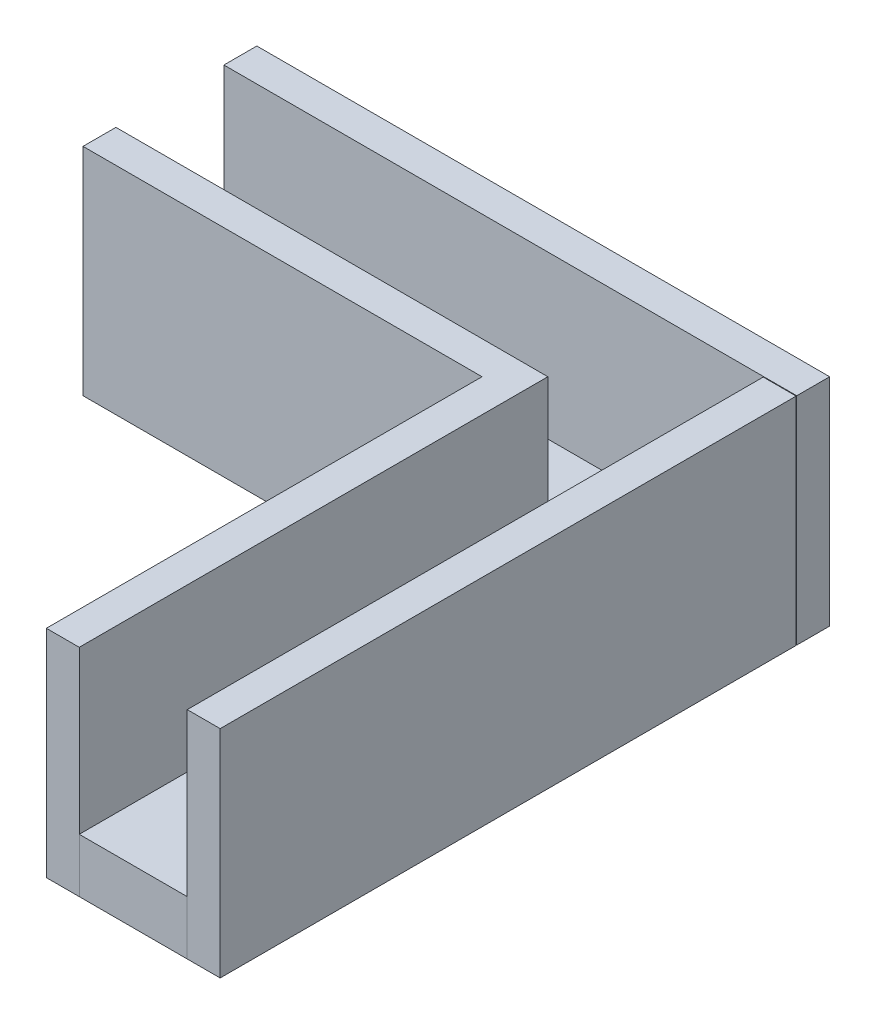
SolidWorks part; units mm, degrees
ref_plane "Front Plane" through (0, 0, 0) normal (0, 0, 1) x (1, 0, 0)
ref_plane "Top Plane" through (0, 0, 0) normal (0, 1, 0) x (1, 0, 0)
ref_plane "Right Plane" through (0, 0, 0) normal (1, 0, 0) x (0, 0, -1)
sketch "Sketch1" plane through (0, 0, 0) normal (0, 1, 0) x (1, 0, 0)
  line L5 (-12.5, 2.5) -> (12.5, -2.5) construction
  line L6 (-12.5, -2.5) -> (12.5, 2.5) construction
  line L7 (12.5, -2.5) -> (7.5, -2.5)
  line L8 (12.5, -2.5) -> (12.5, -24.198)
  line L9 (12.5, -24.198) -> (7.5, -24.198)
  line L10 (7.5, -2.5) -> (7.5, -24.198)
  line L11 (12.5, -24.198) -> (14.024, -24.198)
  line L12 (12.5, -24.198) -> (12.5, 2.472)
  line L13 (12.5, 2.472) -> (14.024, 2.472)
  line L14 (14.024, -24.198) -> (14.024, 2.472)
  line L19 (7.5, -2.5) -> (-12.5, -2.5)
  line L20 (7.5, -2.5) -> (7.5, -4.024)
  line L21 (7.5, -4.024) -> (-12.5, -4.024)
  line L22 (-12.5, -2.5) -> (-12.5, -4.024)
  line L23 (7.5, -24.198) -> (5.976, -24.198)
  line L24 (7.5, -24.198) -> (7.5, -4.024)
  line L25 (7.5, -4.024) -> (5.976, -4.024)
  line L26 (5.976, -24.198) -> (5.976, -4.024)
  line L27 (-12.5, -2.5) -> (12.5, -2.5)
  line L28 (-12.5, -2.5) -> (-12.5, 2.5)
  line L29 (-12.5, 2.5) -> (12.5, 2.5)
  line L30 (12.5, -2.5) -> (12.5, 2.5)
  line L35 (-12.5, 2.5) -> (14.024, 2.5)
  line L36 (-12.5, 2.5) -> (-12.5, 4.024)
  line L37 (-12.5, 4.024) -> (14.024, 4.024)
  line L38 (14.024, 2.5) -> (14.024, 4.024)
  point P0 (0, 0)
  dimension "D1" = 5
  dimension "D2" = 5
  dimension "D3" = 25
  dimension "D4" = 21.698
  dimension "D5" = 1.524
  dimension "D6" = 26.67
  dimension "D7" = 1.524
  dimension "D8" = 1.524
  dimension "D9" = 1.524
extrude "Boss-Extrude3" add sketch "Sketch1" along normal blind 2.5 contours L7 L10 L9 L8 | L12 L30 L29 L28 L19 L7 region at (10, 0, 13.349) region at (0, 0, 0)
extrude "Boss-Extrude4" add sketch "Sketch1<11>" along normal blind 10 separate body contours L11 L14 L13 L12 | L24 L23 L26 L25 | L20 L19 L22 L21 | L35 L38 L37 L36
sketch "Sketch1<11>" plane through (0, 0, 0) normal (0, 1, 0) x (1, 0, 0) same geometry as "Sketch1"
